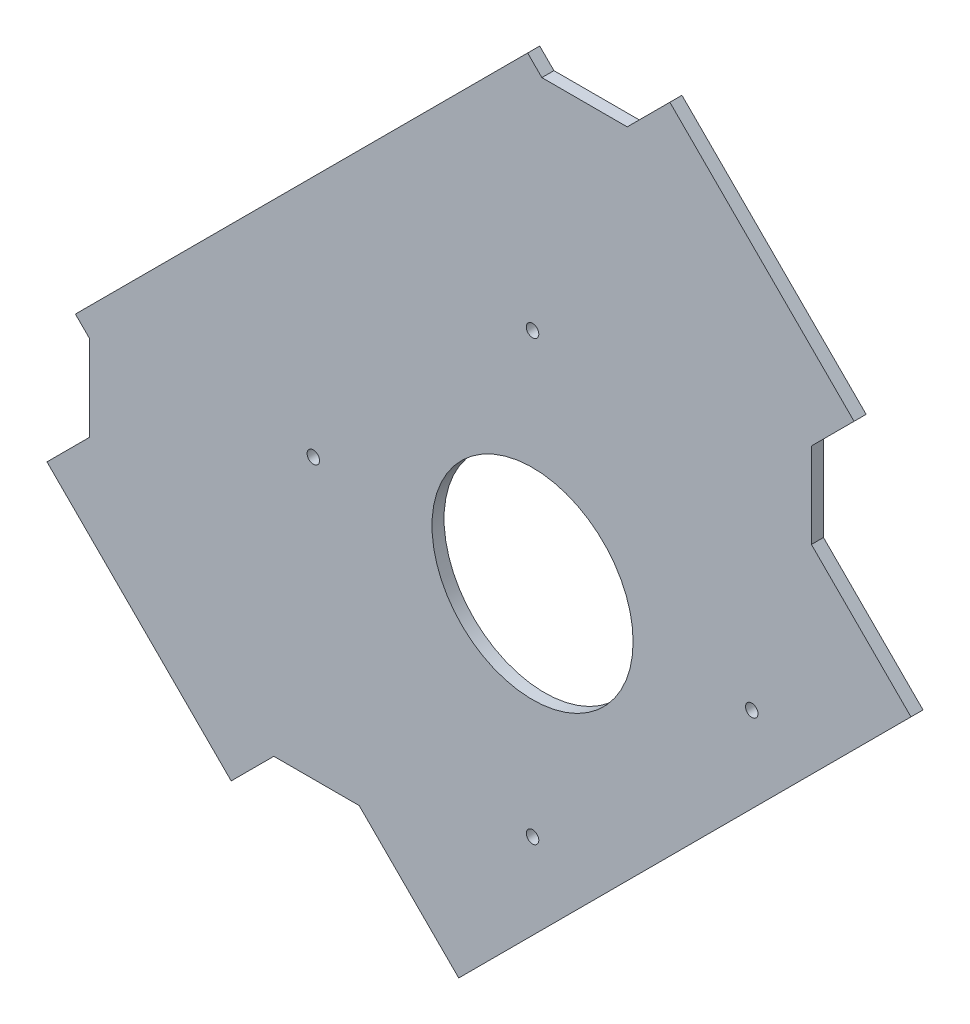
SolidWorks part; units mm, degrees
ref_plane "前视基准面" through (0, 0, 0) normal (0, 0, 1) x (1, 0, 0)
ref_plane "上视基准面" through (0, 0, 0) normal (0, 1, 0) x (1, 0, 0)
ref_plane "右视基准面" through (0, 0, 0) normal (1, 0, 0) x (0, 0, -1)
sketch "Sketch1" plane through (0, 0, 0) normal (0, 0, 1) x (1, 0, 0)
  line L0 (34.1359, 120.7204) -> (79.9357, 74.9206)
  line L1 (34.1359, 120.7204) -> (12.9227, 99.5072)
  line L2 (79.9357, 74.9206) -> (58.7225, 53.7074)
  line L3 (-120.7204, -34.1359) -> (-74.9206, -79.9357)
  line L4 (-1.2195, 113.6493) -> (-113.6493, 1.2195)
  line L5 (-1.2195, 113.6493) -> (12.9227, 99.5072)
  line L6 (-113.6493, 1.2195) -> (-99.5072, -12.9227)
  line L7 (94.0778, 18.352) -> (-18.352, -94.0778)
  line L8 (96.4024, 83.6745) -> (41.2481, 138.8288) construction
  line L9 (109.2209, 52.7064) -> (98.6413, 63.286) construction
  line L10 (-52.7064, -109.2209) -> (-63.286, -98.6413) construction
  line L11 (58.7225, 53.7074) -> (94.0778, 18.352)
  line L12 (-99.5072, -12.9227) -> (-120.7204, -34.1359)
  line L13 (-53.7074, -58.7225) -> (-74.9206, -79.9357)
  line L14 (-53.7074, -58.7225) -> (-18.352, -94.0778)
  circle A0 centre (0, -54.5) radius 1.55 construction
  circle A1 centre (54.5, 0) radius 1.55 construction
  circle A2 centre (-54.5, 0) radius 1.55 construction
  circle A3 centre (0, 54.5) radius 1.55 construction
  circle A4 centre (0, -54.5) radius 1.55
  circle A5 centre (54.5, 0) radius 1.55
  circle A6 centre (-54.5, 0) radius 1.55
  circle A7 centre (0, 54.5) radius 1.55
  circle A8 centre (0, 0) radius 25
  dimension "D1" = 5
  dimension "D2" = 5
  dimension "D3" = 20
  dimension "D4" = 50
  dimension "D5" = 30
  dimension "D6" = 30
extrude "Extrude1" add sketch "Sketch1" along normal blind 3
chamfer "Chamfer1" distance 15 angle 45 4 edges at (12.9227, 99.5072, 1.5) (58.7225, 53.7074, 1.5) (-53.7074, -58.7225, 1.5) (-99.5072, -12.9227, 1.5)
